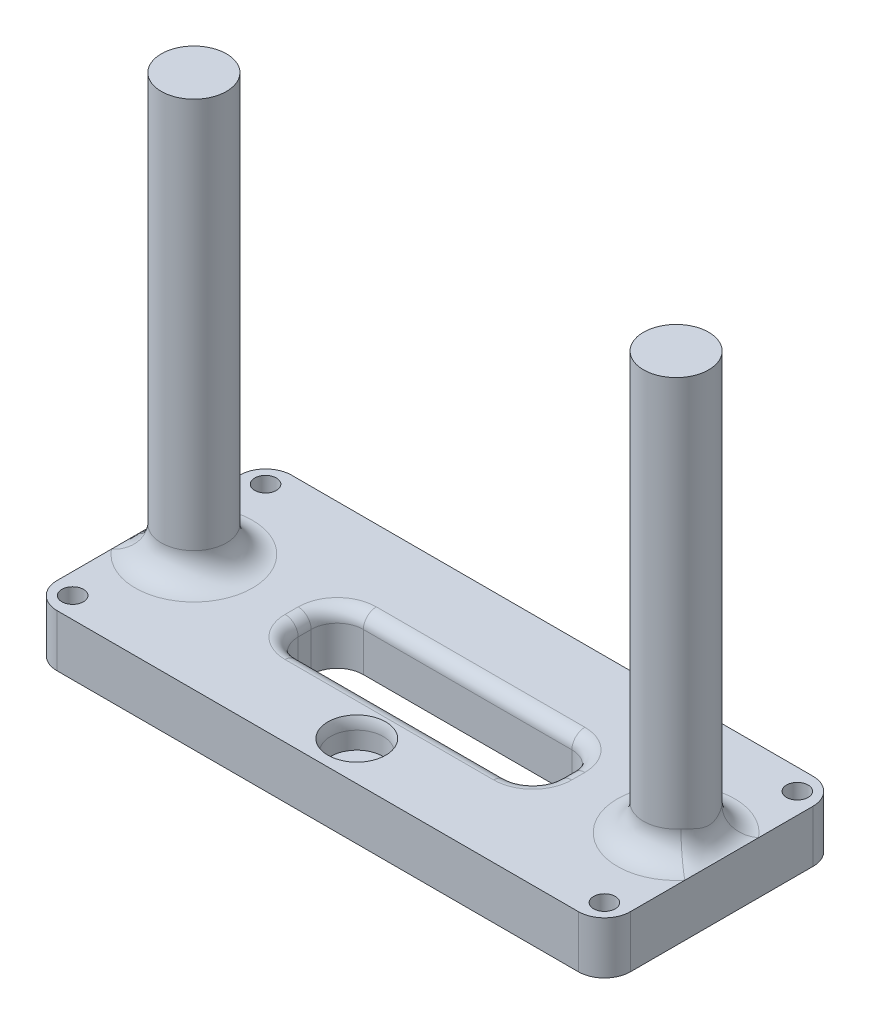
SolidWorks part; units mm, degrees
ref_plane "Front Plane" through (0, 0, 0) normal (0, 0, 1) x (1, 0, 0)
ref_plane "Top Plane" through (0, 0, 0) normal (0, 1, 0) x (1, 0, 0)
ref_plane "Right Plane" through (0, 0, 0) normal (1, 0, 0) x (0, 0, -1)
sketch "Sketch1" plane through (0, 0, 0) normal (0, 1, 0) x (1, 0, 0)
  line L1 (0, 0) -> (220, 0)
  line L2 (0, 0) -> (0, 90)
  line L3 (0, 90) -> (220, 90)
  line L4 (220, 0) -> (220, 90)
  dimension "D1" = 220
  dimension "D2" = 90
extrude "Boss-Extrude1" add sketch "Sketch1" along normal blind 20
sketch "Sketch2" plane through (0, 20, 0) normal (0, 1, 0) x (1, 0, 0)
  line L3 (110, 90) -> (110, 0) construction
  line L4 (220, 90) -> (0, 90) construction
  line L5 (0, 0) -> (220, 0) construction
  circle A0 centre (110, 15) radius 10.1
  dimension "D1" = 20.2
  dimension "D2" = 15
extrude "Cut-Extrude1" cut sketch "Sketch2" against normal blind 11
sketch "Sketch3" plane through (0, 20, 0) normal (0, 1, 0) x (1, 0, 0)
  line L0 (35, 15) -> (185, 15) construction
  line L1 (110, 90) -> (110, 0) construction
  line L2 (220, 90) -> (0, 90) construction
  line L3 (0, 0) -> (220, 0) construction
  circle A0 centre (17.5, 45) radius 12.5
  circle A1 centre (202.5, 45) radius 12.5
  point P4 (110, 15)
  point P9 (110, 15)
  point P15 (110, 45)
  dimension "D1" = 25
  dimension "D2" = 92.5
  dimension "D3" = 150
  dimension "D4" = 92.5
extrude "Boss-Extrude2" add sketch "Sketch3" along normal blind 160
fillet "Fillet2" radius 10 2 edges at (202.5, 20, -57.5) (17.5, 20, -57.5)
fillet "Fillet4" radius 10 4 edges at (220, 10, -90) (220, 10, 0) (0, 10, 0) (0, 10, -90)
chamfer "Chamfer1" distance 1 angle 45 1 edges at (110, 20, -4.9)
fillet "Fillet5" radius 10 1 edges at (110, 19, -25.1)
sketch "Sketch6" plane through (0, 20, 0) normal (0, 1, 0) x (1, 0, 0)
  line L1 (60, 57.5) -> (160, 57.5)
  line L2 (60, 57.5) -> (60, 32.5)
  line L3 (60, 32.5) -> (160, 32.5)
  line L4 (160, 57.5) -> (160, 32.5)
  line L5 (60, 57.5) -> (160, 32.5) construction
  line L6 (60, 32.5) -> (160, 57.5) construction
  point P0 (110, 45)
  point P5 (110, 15)
  point P6 (202.5, 45)
  dimension "D1" = 25
  dimension "D2" = 100
extrude "Cut-Extrude3" cut sketch "Sketch6" against normal through all
fillet "Fillet6" radius 10 4 edges at (60, 10, -32.5) (60, 10, -57.5) (160, 10, -57.5) (160, 10, -32.5)
fillet "Fillet7" radius 5 8 edges at (157.0711, 20, -54.5711) (160, 20, -45) (157.0711, 20, -35.4289) (110, 20, -32.5) (62.9289, 20, -35.4289) (60, 20, -45) (62.9289, 20, -54.5711) (110, 20, -57.5)
sketch "Sketch7" plane through (0, 20, 0) normal (0, 1, 0) x (1, 0, 0)
  line L0 (2.9289, 87.0711) -> (217.0711, 2.9289) construction
  line L1 (2.9289, 2.9289) -> (217.0711, 87.0711) construction
  line L2 (110, 45) -> (138.063, 45) construction
  line L3 (110, 45) -> (110, 71.0776) construction
  circle A1 centre (212, 82) radius 1.88
  arc A2 (10, 90) -> (0, 80) centre (10, 80) ccw construction
  arc A3 (210, 0) -> (220, 10) centre (210, 10) ccw construction
  arc A4 (0, 10) -> (10, 0) centre (10, 10) ccw construction
  arc A5 (220, 80) -> (210, 90) centre (210, 80) ccw construction
  circle A6 centre (212, 8) radius 1.88
  circle A7 centre (8, 8) radius 1.88
  circle A8 centre (8, 82) radius 1.88
  point P1 (0, 0)
  point P20 (110, 45)
  dimension "D1" = 212
  dimension "D3" = 3.76
  dimension "D2" = 82
extrude "Cut-Extrude4" cut sketch "Sketch7" against normal through all
sketch "Sketch8" plane through (0, 20, 0) normal (0, 1, 0) x (1, 0, 0)
  circle A0 centre (212, 82) radius 4.15
  circle A1 centre (212, 8) radius 4.15
  circle A2 centre (8, 8) radius 4.15
  circle A3 centre (8, 82) radius 4.15
  dimension "D1" = 8.3
extrude "Cut-Extrude5" cut sketch "Sketch8" against normal offset from surface (10 mm away) 10 up to face at (8, 0, -83.88)
